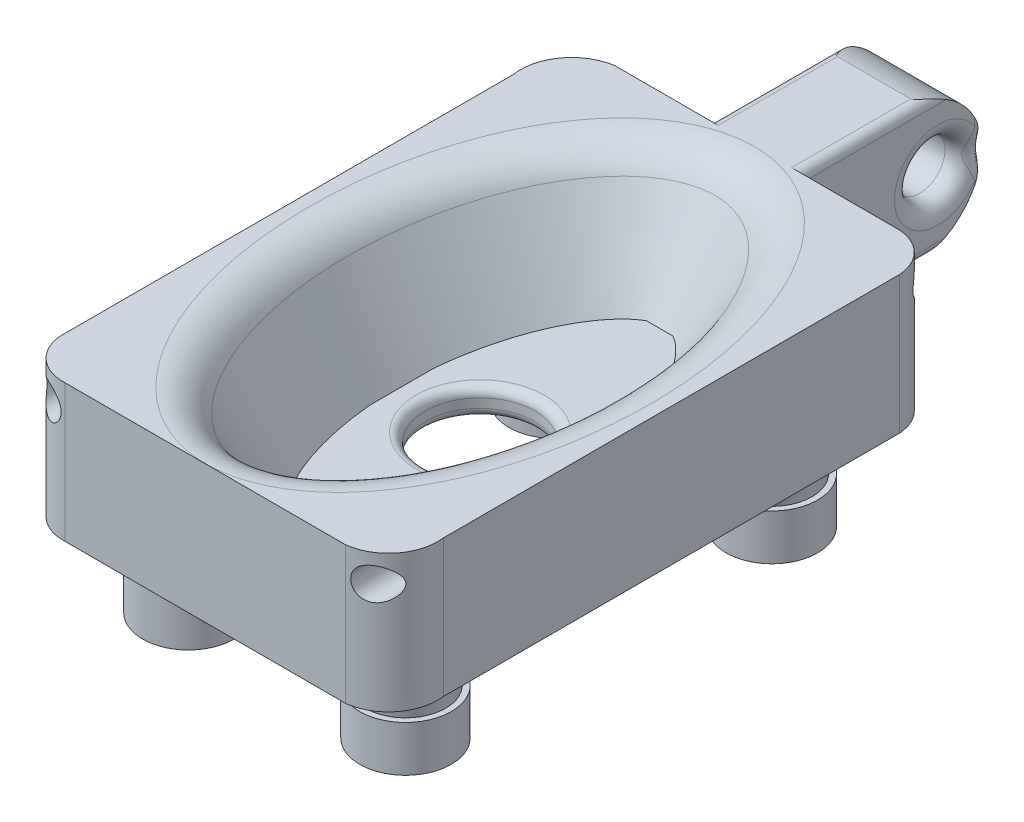
SolidWorks part; units mm, degrees
ref_plane "Front Plane" through (0, 0, 0) normal (0, 0, 1) x (1, 0, 0)
ref_plane "Top Plane" through (0, 0, 0) normal (0, 1, 0) x (1, 0, 0)
ref_plane "Right Plane" through (0, 0, 0) normal (1, 0, 0) x (0, 0, -1)
sketch "Sketch1" plane through (0, 0, 0) normal (0, 1, 0) x (1, 0, 0)
  line L1 (-15.3125, -30) -> (15.3125, -30)
  line L2 (-20, -25.7813) -> (-20, 23.5937)
  line L3 (-15.3125, 30) -> (15.3125, 30)
  line L4 (20, -24.0015) -> (20, 25.7812)
  line L5 (-20, -30) -> (20, 30) construction
  line L6 (-20, 30) -> (20, -30) construction
  arc A0 (-15.3125, 30) -> (-20, 23.5937) centre (-14.4531, 24.4531) ccw
  arc A1 (15.3125, 30) -> (20, 25.7812) centre (15.5469, 25.5469) cw
  arc A2 (15.3125, -30) -> (20, -24.0015) centre (14.657, -24.657) ccw
  arc A3 (-15.3125, -30) -> (-20, -25.7813) centre (-15.5469, -25.5469) cw
  point P0 (0, 0)
  dimension "D1" = 40
  dimension "D2" = 60
extrude "Boss-Extrude1" add sketch "Sketch1" along normal blind 15
sketch "Sketch2" plane through (0, 0, 30) normal (0, 0, 1) x (1, 0, 0)
  line L0 (-20, 15) -> (-20, 0) construction
  line L1 (20.0401, 0) -> (20.0401, 15) construction
  line L2 (15.3125, 0) -> (20.0401, 0) construction
  line L3 (-20, 0) -> (-15.3125, 0) construction
  circle A0 centre (-17.5, 12) radius 1.75
  circle A1 centre (17.5401, 12) radius 1.75
  dimension "D1" = 2.5
  dimension "D5" = 3.5
  dimension "D6" = 3.5
  dimension "D2" = 2.5
  dimension "D3" = 12
  dimension "D4" = 12
sketch "Sketch4" plane through (0, 15, 0) normal (0, 1, 0) x (1, 0, 0)
  ellipse E0 centre (0, 0) end of major axis (0, 27.1105) minor radius 15.7856
extrude "Cut-Extrude6" cut sketch "Sketch4" against normal blind 15 draft 30.5
fillet "Fillet4" radius 5 1 edges at (-2.7969, 15, -26.6816) type face fillet first side face at (-0.082, 0, -18.2666) second side face at (-2.7969, 15, -26.6816)
extrude "Cut-Extrude7" cut sketch "Sketch2" against normal blind 150
sketch "Sketch5" plane through (0, 0, 0) normal (0, -1, 0) x (1, 0, 0)
  line L1 (7.7139, -19.6019) -> (-8.5645, -19.6019)
  line L2 (7.7139, -19.6019) -> (7.7139, 20.1727)
  line L3 (7.7139, 20.1727) -> (-8.5645, 20.1727)
  line L4 (-8.5645, -19.6019) -> (-8.5645, 20.1727)
extrude "Boss-Extrude2" add sketch "Sketch5" against normal blind 3
sketch "Sketch6" plane through (0, 3, 0) normal (0, 1, 0) x (1, 0, 0)
  circle A0 centre (0, 0) radius 6
extrude "Cut-Extrude8" cut sketch "Sketch6" against normal blind 3
sketch "Sketch8" plane through (0, 0, -30) normal (0, 0, -1) x (-1, 0, 0)
  line L7 (-5, 15) -> (5, 15)
  line L8 (-5, 15) -> (-5, 0)
  line L9 (-5, 0) -> (5, 0)
  line L10 (5, 15) -> (5, 0)
  point P9 (0, 7.5)
extrude "Boss-Extrude3" add sketch "Sketch8" along normal blind 20
sketch "Sketch10" plane through (-5, 0, 0) normal (-1, 0, 0) x (0, 0, 1)
  line L0 (-50, 0) -> (-50, 15) construction
  line L1 (-50, 15) -> (-30, 15) construction
  circle A0 centre (-45, 7.32) radius 2.75
  dimension "D1" = 5
  dimension "D3" = 5.5
  dimension "D2" = 7.68
extrude "Cut-Extrude9" cut sketch "Sketch10" against normal blind 20
fillet "Fillet8" radius 2 1 edges at (5, 4.57, -45) type face fillet first side face at (5, 4.57, -45) second side face at (-5, 4.57, -45)
fillet "Fillet9" radius 1 1 edges at (-5, 4.57, -45) type face fillet first side face at (-5, 4.57, -45) second side face at (3, 4.57, -45)
fillet "Fillet11" radius 1 1 edges at (0, 15, -50) type face fillet first side face at (0, 7.5, -50) second side face at (-1.6146, 15, 29.8598)
fillet "Fillet12" radius 1 1 edges at (-5, 15, -39.5) type face fillet first side face at (-5, 11.07, -45) second side face at (-1.6146, 15, 29.8598)
fillet "Fillet13" radius 1 1 edges at (5, 15, -39.5) type face fillet first side face at (5, 2.57, -45) second side face at (-1.6146, 15, 29.8598)
fillet "Fillet14" radius 1 1 edges at (5, 0, -39.5) type face fillet first side face at (0, 0, 6) second side face at (5, 7.1067, -41.2083)
fillet "Fillet29" radius 1 1 edges at (0, 0, 6) type face fillet first side face at (0, 0, 6) second side face at (0, 0, 6)
fillet "Fillet30" radius 1 1 edges at (0, 3, 6) type face fillet first side face at (0, 3, 6) second side face at (0, 1, 6)
sketch "Sketch11" plane through (0, 0, 0) normal (0, -1, 0) x (1, 0, 0)
  line L0 (-20, -23.5937) -> (-20, 25.7813) construction
  line L1 (20, 24.0015) -> (20, -25.7812) construction
  circle A0 centre (-11.85, 20) radius 5
  circle A1 centre (11.85, 20) radius 5
  circle A2 centre (-11.85, -20) radius 5
  circle A3 centre (11.85, -20) radius 5
  dimension "D1" = 10
  dimension "D2" = 10
  dimension "D3" = 10
  dimension "D4" = 10
  dimension "D5" = 8.15
  dimension "D6" = 8.15
  dimension "D7" = 8.15
  dimension "D8" = 8.15
  dimension "D9" = 20
  dimension "D10" = 20
  dimension "D11" = 20
  dimension "D12" = 20
extrude "Boss-Extrude4" add sketch "Sketch11" along normal blind 5 draft 7
sketch "Sketch12" plane through (0, -5, 0) normal (0, -1, 0) x (1, 0, 0)
  circle A0 centre (-11.85, 20) radius 5
  circle A1 centre (11.85, 20) radius 5
  circle A2 centre (-11.85, -20) radius 5
  circle A3 centre (11.85, -20) radius 5
  dimension "D1" = 10
  dimension "D2" = 10
  dimension "D3" = 10
  dimension "D4" = 10
extrude "Boss-Extrude5" add sketch "Sketch12" along normal blind 5
sketch "Sketch17" plane through (5, 0, 0) normal (1, 0, 0) x (0, 0, -1)
  line L0 (49, 0) -> (30, 0) construction
  line L1 (49.8976, 15.0667) -> (41.3258, 15.0667)
  line L3 (49.8976, 0) -> (41.3258, 0)
  line L6 (49.8976, 15.0667) -> (50.7875, 15.0667)
  line L7 (49.8976, 7.5333) -> (49.8976, 0)
  line L8 (49.8976, 0) -> (50.7875, 0)
  line L9 (50.7875, 15.0667) -> (50.7875, 0)
  arc A0 (49.8976, 7.5333) -> (41.3258, 0) centre (41.845, 8.0525) cw
  arc A1 (41.3258, 15.0667) -> (49.8976, 7.5333) centre (41.845, 7.0141) cw
  line M10 (30, 1) -> (49, 1)
  line M11 (49, 1) -> (49, 4.7583)
  line M13 (49, 9.8817) -> (49, 14)
  line M14 (49, 14) -> (30, 14)
extrude "Cut-Extrude12" cut sketch "Sketch17" against normal blind 25 contours A1 M14 M13 | A1 L7 L8 L9 L6 L1 M13 M14 | A0 M11 M10 | L7 A0 L3 M11 M10 region at (5, 9.9808, -49.4216) region at (5, 13.022, -48.0618) region at (5, 0.1065, -46.1309) region at (5, 1.9951, -48.03)
